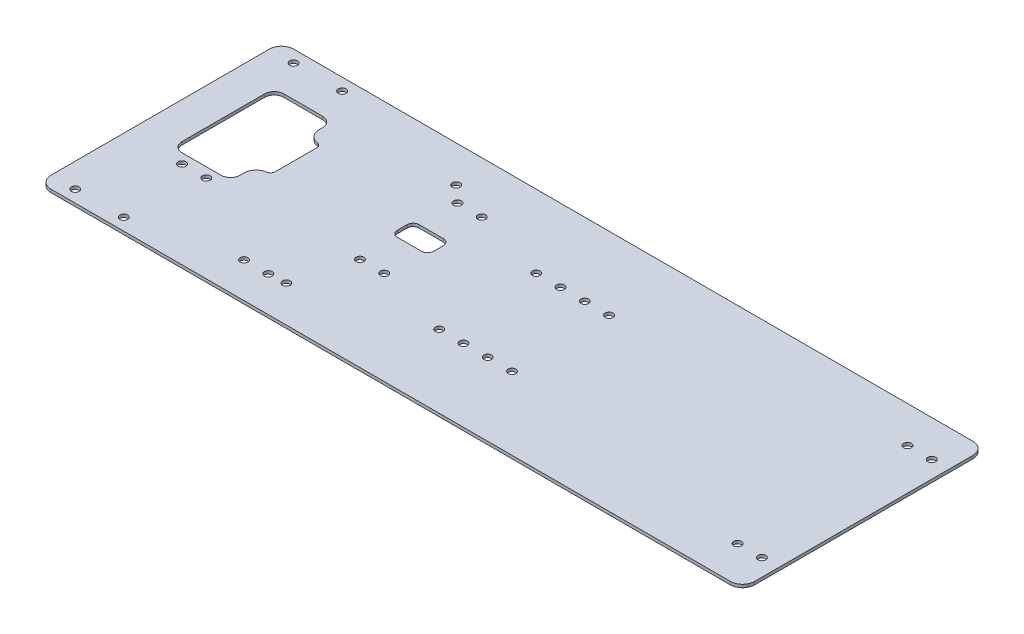
SolidWorks part; units mm, degrees
ref_plane "Front Plane" through (0, 0, 0) normal (0, 0, 1) x (1, 0, 0)
ref_plane "Top Plane" through (0, 0, 0) normal (0, 1, 0) x (1, 0, 0)
ref_plane "Right Plane" through (0, 0, 0) normal (1, 0, 0) x (0, 0, -1)
sketch "Sketch1" plane through (0, 0, 0) normal (0, 1, 0) x (1, 0, 0)
  line L0 (128.27, 0) -> (-128.27, 0) construction
  line L1 (184.15, 63.5) -> (-184.15, 63.5)
  line L2 (184.15, 63.5) -> (184.15, -63.5)
  line L3 (184.15, -63.5) -> (-184.15, -63.5)
  line L4 (-184.15, 63.5) -> (-184.15, -63.5)
  line L5 (184.15, 63.5) -> (-184.15, -63.5) construction
  line L6 (184.15, -63.5) -> (-184.15, 63.5) construction
  line L7 (-128.27, 0) -> (-128.27, 31.75) construction
  line L8 (-128.27, 31.75) -> (-134.62, 31.75) construction
  line L9 (-128.27, 6.35) -> (-134.62, 6.35) construction
  line L12 (-165.1, -12.7) -> (-165.1, 40.64)
  line L15 (-134.62, -12.7) -> (-165.1, -12.7)
  line L17 (-134.62, 40.64) -> (-165.1, 40.64)
  line L18 (0, 63.5) -> (0, -63.5) construction
  line L19 (-134.62, 40.64) -> (-134.62, -12.7)
  line L21 (-95.25, -45.0215) -> (-95.25, -32.3215) construction
  line L22 (-82.55, -45.0215) -> (-95.25, -45.0215) construction
  line L25 (128.27, 31.75) -> (128.27, 6.35) construction
  line L26 (-95.25, -32.3215) -> (-82.55, -32.3215) construction
  line L30 (-82.55, -32.3215) -> (-82.55, -45.0215) construction
  line L31 (184.15, -17.78) -> (154.94, -17.78) construction
  line L32 (146.05, 57.15) -> (184.15, 57.15) construction
  line L33 (154.94, -17.78) -> (142.24, -17.78) construction
  line L34 (146.05, -57.15) -> (184.15, -57.15) construction
  line L35 (-146.05, -57.15) -> (-184.15, -57.15) construction
  line L36 (-146.05, 57.15) -> (-184.15, 57.15) construction
  line L37 (-128.27, 0) -> (-128.27, 6.35) construction
  line L38 (-184.15, -17.78) -> (-154.94, -17.78) construction
  line L39 (-154.94, -17.78) -> (-142.24, -17.78) construction
  line L40 (-134.62, 27.305) -> (-127, 27.305)
  line L41 (-127, 27.305) -> (-127, 0.635)
  line L42 (-127, 0.635) -> (-134.62, 0.635)
  circle A4 centre (171.45, 31.75) radius 2.032 construction
  circle A5 centre (128.27, 31.75) radius 2.032 construction
  circle A6 centre (128.27, 6.35) radius 2.032 construction
  circle A7 centre (171.45, -3.81) radius 2.032 construction
  circle A8 centre (171.45, -57.15) radius 2.032
  circle A9 centre (146.05, -57.15) radius 2.032
  circle A10 centre (171.45, 57.15) radius 2.032
  circle A11 centre (146.05, 57.15) radius 2.032
  circle A12 centre (-146.05, -57.15) radius 2.032
  circle A13 centre (-171.45, -57.15) radius 2.032
  circle A14 centre (-146.05, 57.15) radius 2.032
  circle A15 centre (-171.45, 57.15) radius 2.032
  circle A16 centre (142.24, -17.78) radius 2.032 construction
  circle A17 centre (154.94, -17.78) radius 2.032 construction
  circle A18 centre (-154.94, -17.78) radius 2.032
  circle A19 centre (-142.24, -17.78) radius 2.032
  circle A20 centre (-95.25, -45.0215) radius 2.032
  circle A21 centre (-82.55, -45.0215) radius 2.032
  circle A22 centre (-95.25, -32.3215) radius 2.032
  circle A23 centre (-82.55, -32.3215) radius 2.032
  point P0 (0, 0)
  point P11 (-128.27, 0)
  point P13 (-134.62, 31.75)
  point P17 (-134.62, 6.35)
  point P37 (0, 0)
  point P50 (171.45, 57.15)
  point P51 (146.05, 57.15)
  point P56 (171.45, -57.15)
  point P57 (146.05, -57.15)
  point P84 (-130.81, 27.305)
  point P87 (130.81, 27.305)
  dimension "D5" = 13.335
  dimension "D18" = 4.064
  dimension "D1" = 368.3
  dimension "D2" = 127
  dimension "D3" = 128.27
  dimension "D4" = 25.4
  dimension "D7" = 6.35
  dimension "D8" = 30.48
  dimension "D9" = 53.34
  dimension "D10" = 8.89
  dimension "D11" = 19.05
  dimension "D14" = 12.7
  dimension "D15" = 38.1
  dimension "D16" = 12.7
  dimension "D17" = 38.1
  dimension "D19" = 31.75
  dimension "D20" = 6.35
  dimension "D21" = 6.35
  dimension "D22" = 5.08
  dimension "D23" = 29.21
  dimension "D24" = 12.7
  dimension "D25" = 88.9
  dimension "D26" = 12.7
  dimension "D27" = 7.62
  dimension "D28" = 26.67
  dimension "D29" = 13.335
  dimension "D30" = 18.4785
  dimension "D31" = 12.7
extrude "Boss-Extrude1" add sketch "Sketch1" along normal blind 1.5875 contours L1 L4 L3 L2 A23 A22 A21 A20 A18 A14 A12 A11 A10 A9 A8 L41 L42 L19 L15 L12 L17 L40 A13 A15 A19 | A9 | A8 | A11 | A10 | A22 | A23 region at (6.2259, 0, 0.5157) region at (171.45, 0, 57.15) region at (146.05, 0, 57.15) region at (171.45, 0, -57.15) region at (146.05, 0, -57.15) region at (-95.25, 0, 32.3215) region at (-82.55, 0, 32.3215)
sketch "Sketch2" [suppressed] plane through (0, 1.5875, 0) normal (0, 1, 0) x (1, 0, 0)
  line L0 (-69.85, 63.5) -> (-69.85, -63.5)
  line L1 (184.15, 63.5) -> (-184.15, 63.5) construction
  line L2 (184.15, -63.5) -> (-184.15, -63.5) construction
  circle A0 centre (-82.55, -45.0215) radius 2.032 construction
  circle M9 centre (146.05, 57.15) radius 2.032
  circle M10 centre (171.45, 57.15) radius 2.032
  circle M11 centre (146.05, -57.15) radius 2.032
  circle M12 centre (171.45, -57.15) radius 2.032
  line M13 (184.15, 63.5) -> (-184.15, 63.5)
  line M15 (-184.15, -63.5) -> (184.15, -63.5)
  line M16 (184.15, -63.5) -> (184.15, 63.5)
  dimension "D1" = 12.7
extrude "Cut-Extrude1" [suppressed] cut sketch "Sketch2" against normal through all flip side to cut contours L0 M13 M15 M16 M10 M12 M11 M9
fillet "Fillet1" radius 5.08 4 edges at (-134.62, 0.7937, 12.7) (-165.1, 0.7937, 12.7) (-165.1, 0.7937, -40.64) (-134.62, 0.7937, -40.64)
fillet "Fillet3" radius 6.35 4 edges at (184.15, 0.7937, 63.5) (184.15, 0.7937, -63.5) (-184.15, 0.7937, 63.5) (-184.15, 0.7937, -63.5)
fillet "Fillet4" radius 2.54 2 edges at (-127, 0.7937, -0.635) (-127, 0.7937, -27.305)
fillet "Fillet5" radius 6.35 2 edges at (-134.62, 0.7937, -0.635) (-134.62, 0.7937, -27.305)
fillet "Fillet6" [suppressed] radius 6.35
sketch "Sketch3" plane through (0, 1.5875, 0) normal (0, 1, 0) x (1, 0, 0)
  arc A2 (10.7648, -26.0196) -> (10.7648, -24.7804) centre (12.7, -25.4) ccw construction
  circle A3 centre (25.4, -25.4) radius 2.032 construction
  circle A4 centre (25.4, 25.4) radius 2.032 construction
  arc A5 (10.7648, 24.7804) -> (10.7648, 26.0196) centre (12.7, 25.4) ccw construction
  circle A9 centre (162.56, -44.45) radius 2.032 construction
  circle A10 centre (162.56, 44.45) radius 2.032 construction
  circle A12 centre (0, -25.4) radius 2.032 construction
  circle A15 centre (-73.66, 44.45) radius 2.032 construction
  circle A16 centre (-73.66, -44.45) radius 2.032 construction
  circle A17 centre (25.4, -25.4) radius 2.032
  circle A18 centre (25.4, 25.4) radius 2.032
  circle A19 centre (-12.7, -25.4) radius 2.032 construction
  circle A20 centre (-12.7, 25.4) radius 2.032 construction
  circle A23 centre (162.56, -44.45) radius 2.032
  circle A24 centre (162.56, 44.45) radius 2.032
  circle A28 centre (0, -25.4) radius 2.032
  circle A29 centre (12.7, -25.4) radius 2.032
  circle A30 centre (0, 25.4) radius 2.032
  circle A31 centre (12.7, 25.4) radius 2.032
  circle A32 centre (175.26, 44.45) radius 2.032 construction
  circle A33 centre (175.26, -44.45) radius 2.032 construction
  circle A34 centre (175.26, 44.45) radius 2.032
  circle A35 centre (175.26, -44.45) radius 2.032
  circle A36 centre (0, 25.4) radius 2.032 construction
  circle A41 centre (0, -25.4) radius 2.032
  circle A42 centre (0, 25.4) radius 2.032
  circle A54 centre (-73.66, 44.45) radius 2.032
  circle A55 centre (-73.66, -44.45) radius 2.032
  circle A56 centre (-12.7, -25.4) radius 2.032
  circle A57 centre (-12.7, 25.4) radius 2.032
extrude "Cut-Extrude5" cut sketch "Sketch3" against normal through all contours A24 | A28 | A29 | A30 | A31 | A17 | A18 | A23 | A35 | A34 | A55 | A56 | A57 | A54 region at (162.56, 1.5875, -44.45) region at (0, 1.5875, 25.4) region at (12.7, 1.5875, 25.4) region at (0, 1.5875, -25.4) region at (12.7, 1.5875, -25.4)
sketch "Sketch4" plane through (0, 1.5875, 0) normal (0, 1, 0) x (1, 0, 0)
  line L0 (-50.9125, -11.9075) -> (-66.7875, -11.9075) construction
  line L1 (-66.7875, -17.0193) -> (-50.9125, -17.0193) construction
  line L2 (-66.7875, 38.758) -> (-50.9125, 38.758) construction
  line L3 (-50.9125, 34.44) -> (-66.7875, 34.44) construction
  line L4 (-50.9125, -11.9075) -> (-66.7875, -11.9075)
  line L5 (-66.7875, -17.0193) -> (-50.9125, -17.0193)
  line L6 (-66.7875, 38.758) -> (-50.9125, 38.758)
  line L7 (-50.9125, 34.44) -> (-66.7875, 34.44)
  line L8 (-66.7875, 36.599) -> (-50.9125, 36.599) construction
  line L9 (-66.7875, -14.4634) -> (-50.9125, -14.4634) construction
  arc A0 (-50.9125, -17.0193) -> (-50.9125, -11.9075) centre (-50.9125, -14.4634) ccw construction
  arc A1 (-66.7875, -11.9075) -> (-66.7875, -17.0193) centre (-66.7875, -14.4634) ccw construction
  arc A3 (-66.7875, 38.758) -> (-66.7875, 34.44) centre (-66.7875, 36.599) ccw construction
  arc A4 (-50.9125, -17.0193) -> (-50.9125, -11.9075) centre (-50.9125, -14.4634) ccw
  arc A5 (-66.7875, -11.9075) -> (-66.7875, -17.0193) centre (-66.7875, -14.4634) ccw
  arc A6 (-50.9125, 34.44) -> (-50.9125, 38.758) centre (-50.9125, 36.599) ccw construction
  arc A7 (-66.7875, 38.758) -> (-66.7875, 34.44) centre (-66.7875, 36.599) ccw
  arc A8 (-50.9125, 34.44) -> (-50.9125, 38.758) centre (-50.9125, 36.599) ccw
  circle A9 centre (-65.1365, 36.599) radius 2.032
  circle A10 centre (-52.4365, 36.599) radius 2.032
  circle A11 centre (-65.1365, -14.4634) radius 2.032
  circle A12 centre (-52.4365, -14.4634) radius 2.032
  dimension "D1" = 4.064
  dimension "D2" = 12.7
  dimension "D3" = 1.651
  dimension "D4" = 12.7
  dimension "D5" = 1.651
extrude "Cut-Extrude6" cut sketch "Sketch4" against normal through all and the other way through all contours A11 | A12 | A10 | A9 region at (-65.1365, 1.5875, -36.599) region at (-52.4365, 1.5875, -36.599) region at (-65.1365, 1.5875, 14.4634) region at (-52.4365, 1.5875, 14.4634)
sketch "Sketch5" plane through (0, 1.5875, 0) normal (0, 1, 0) x (1, 0, 0)
  line L1 (-67.175, 12.0678) -> (-67.175, 10.0678) construction
  line L3 (-67.175, 12.0678) -> (-67.175, 10.0678)
  line L4 (-65.375, 13.8678) -> (-52.675, 13.8678)
  line L5 (-65.375, 8.2678) -> (-52.675, 8.2678)
  line L6 (-50.8769, 10.013) -> (-50.8769, 12.0776)
  line L8 (-65.375, 13.6053) -> (-65.375, 8.5253) construction
  line L9 (-62.2, 13.6053) -> (-62.2, 8.5253)
  line L10 (-68.55, 13.6053) -> (-68.55, 8.5253)
  line L11 (-65.375, 6.9978) -> (-52.6746, 6.9978)
  line L12 (-49.6069, 9.9962) -> (-49.6069, 12.0806)
  line L13 (-65.375, 15.1378) -> (-52.6743, 15.1378)
  line L14 (-68.445, 12.0678) -> (-68.445, 10.0678)
  line L15 (-52.675, 13.5878) -> (-52.675, 8.5078) construction
  line L16 (-49.5, 13.5878) -> (-49.5, 8.5078)
  line L17 (-55.85, 13.5878) -> (-55.85, 8.5078)
  line L18 (-67.175, 11.0678) -> (-50.8769, 11.0453) construction
  line L20 (-65.375, 16.7803) -> (-52.675, 16.7628)
  line L22 (-52.675, 5.3328) -> (-65.375, 5.3503)
  arc A0 (-63.575, 12.0678) -> (-67.175, 12.0678) centre (-65.375, 12.0678) ccw construction
  arc A2 (-67.175, 10.0678) -> (-65.375, 8.2678) centre (-65.375, 10.0678) ccw construction
  arc A3 (-65.375, 13.8678) -> (-67.175, 12.0678) centre (-65.375, 12.0678) ccw
  arc A5 (-67.175, 10.0678) -> (-65.375, 8.2678) centre (-65.375, 10.0678) ccw
  arc A6 (-50.8769, 12.0776) -> (-52.675, 13.8678) centre (-52.6769, 12.0678) ccw
  arc A7 (-52.675, 8.2678) -> (-50.8769, 10.013) centre (-52.6761, 10.0678) ccw
  arc A9 (-62.2, 13.6053) -> (-68.55, 13.6053) centre (-65.375, 13.6053) ccw
  arc A10 (-68.55, 8.5253) -> (-62.2, 8.5253) centre (-65.375, 8.5253) ccw
  arc A11 (-49.5, 13.5878) -> (-55.85, 13.5878) centre (-52.675, 13.5878) ccw
  arc A12 (-52.6746, 6.9978) -> (-49.6069, 9.9962) centre (-52.6761, 10.0678) ccw
  arc A13 (-49.6069, 12.0806) -> (-52.6743, 15.1378) centre (-52.6769, 12.0678) ccw
  arc A14 (-65.375, 15.1378) -> (-68.445, 12.0678) centre (-65.375, 12.0678) ccw
  arc A15 (-68.445, 10.0678) -> (-65.375, 6.9978) centre (-65.375, 10.0678) ccw
  arc A16 (-55.85, 8.5078) -> (-49.5, 8.5078) centre (-52.675, 8.5078) ccw
  point P17 (-65.375, 11.0653)
  point P22 (-52.675, 11.0478)
  dimension "D1" = 16.2981
  dimension "D2" = 12.7
  dimension "D3" = 2.0646
  dimension "D4" = 1.7902
  dimension "D5" = 5.08
  dimension "D7" = 3.175
  dimension "D6" = 1.27
extrude "Cut-Extrude7" cut sketch "Sketch5" against normal through all and the other way through all contours A16 L11 A10 L22 | A16 L5 A10 L11 | A16 L17 A11 L4 A9 L9 A10 L5 | A11 L13 A9 L4 | A11 L20 A9 L13 | A9 L10 A10 L9 | A16 L16 A11 L17 region at (-59.0223, 1.5875, -14.515) region at (-59.025, 1.5875, -11.0679) region at (-59.0276, 1.5875, -7.621) region at (-63.9847, 1.5875, -15.3335) region at (-59.0255, 1.5875, -6.1024)
equation "\".80.55in\"=0.55"
